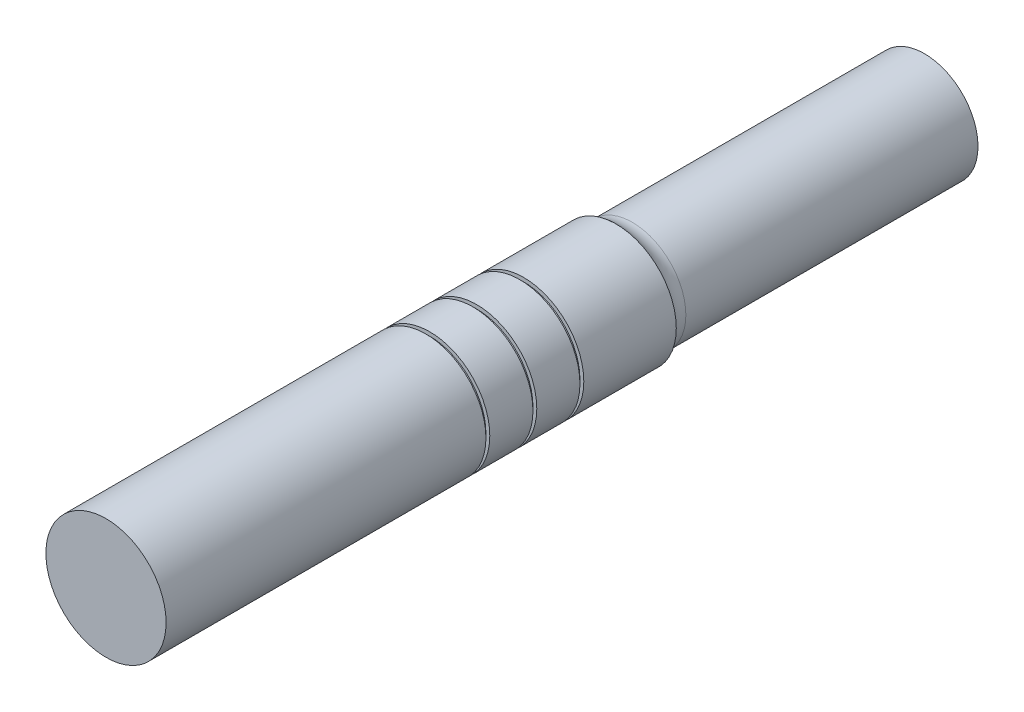
SolidWorks part; units mm, degrees
material "O1 Steel"
ref_plane "Alzado" through (0, 0, 0) normal (0, 0, 1) x (1, 0, 0)
ref_plane "Planta" through (0, 0, 0) normal (0, 1, 0) x (1, 0, 0)
ref_plane "Vista lateral" through (0, 0, 0) normal (1, 0, 0) x (0, 0, -1)
sketch "Croquis1" plane through (0, 0, 0) normal (1, 0, 0) x (0, 0, -1)
  line L0 (-127, 0) -> (127, 0) construction
  line L1 (-13.4874, 0) -> (-13.4874, 1.9812)
  line L3 (0.1524, 1.9812) -> (0.1524, 1.8542)
  line L4 (0.1524, 1.8542) -> (0.2794, 1.8542)
  line L5 (0.2794, 1.8542) -> (0.2794, 1.9812)
  line L10 (0.2794, 1.9812) -> (3.3274, 1.9812)
  line L11 (3.3274, 1.9812) -> (3.3274, 1.7653)
  line L12 (3.3274, 1.7653) -> (13.4874, 1.7653)
  line L13 (13.4874, 1.7653) -> (13.4874, 0)
  line L14 (13.4874, 0) -> (-13.4874, 0)
  line L15 (0.1524, 1.9812) -> (-1.27, 1.9812)
  line L16 (-1.27, 1.9812) -> (-1.27, 1.8542)
  line L17 (-1.27, 1.8542) -> (-1.397, 1.8542)
  line L18 (-1.397, 1.8542) -> (-1.397, 1.9812)
  line L19 (-1.397, 1.9812) -> (-2.8194, 1.9812)
  line L20 (-2.8194, 1.9812) -> (-2.8194, 1.8542)
  line L21 (-2.8194, 1.8542) -> (-2.9464, 1.8542)
  line L22 (-2.9464, 1.8542) -> (-2.9464, 1.9812)
  line L23 (-2.9464, 1.9812) -> (-13.4874, 1.9812)
  point P7 (-1.27, 1.7311)
  point P22 (-1.6611, 1.8562)
  point P23 (-1.4622, 1.8562)
  point P24 (-1.27, 1.8107)
  point P25 (-1.3628, 1.8355)
  point P26 (-2.2254, 1.8089)
  point P27 (-2.4227, 1.8138)
  point P28 (-1.3335, 1.8542)
  point P29 (-2.8829, 1.8542)
  dimension "D1" = 254
  dimension "D2" = 3.9624
  dimension "D3" = 26.9748
  dimension "D4" = 3.5306
  dimension "D5" = 10.16
  dimension "D6" = 3.048
  dimension "D7" = 0.127
  dimension "D8" = 0.127
  dimension "D9" = 1.5494
  dimension "D10" = 1.5494
revolve "Revolución1" add sketch "Croquis1" angle 360 about L0
fillet "Redondeo1" radius 0.762 1 edges at (1.7653, 0, -3.3274)
sketch "Croquis2" plane through (0, 0, -13.4874) normal (0, 0, -1) x (-1, 0, 0)
  point P0 (0, 0)
hole_wizard "Taladro de margen para #101" positions "Croquis2" profile "Croquis3" hole size "#10" standard "Ansi Inch"
sketch "Croquis3" plane through (0, 0, -13.4874) normal (1, 0, 0) x (0, 1, 0)
  line L0 (0, 0) -> (0, 1.5733)
  line L1 (0, 1.5733) -> (1.1811, 0.8636)
  line L2 (1.1811, 0.8636) -> (1.1811, 0)
  line L5 (1.1811, 0) -> (0, 0)
  line L10 (0, 1.5733) -> (-1.1811, 0.8636) construction
  line L11 (0, -6.35) -> (0, 107.95) construction
  dimension "Diámetro de taladro" = 2.3622
  dimension "Profundidad de taladro" = 0.8636
  dimension "Ángulo de perforador" = 118
chamfer "Chaflán1" distance 0.5842 angle 30 1 edges at (-1.1811, 0, -13.4874) first distance on face at (-1.1811, 0, -13.4874)
